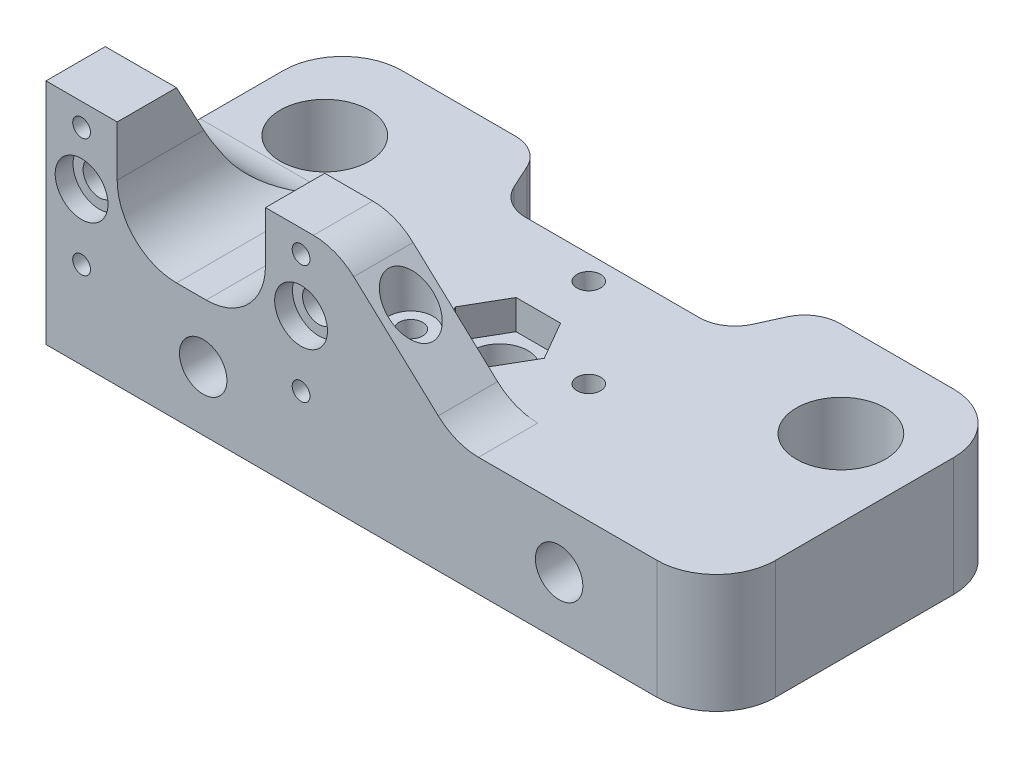
SolidWorks part; units mm, degrees
material "ABS PC"
ref_plane "Front Plane" through (0, 0, 0) normal (0, 0, 1) x (1, 0, 0)
ref_plane "Top Plane" through (0, 0, 0) normal (0, 1, 0) x (1, 0, 0)
ref_plane "Right Plane" through (0, 0, 0) normal (1, 0, 0) x (0, 0, -1)
sketch "Sketch1" plane through (0, 0, 0) normal (0, 1, 0) x (1, 0, 0)
  line L0 (56.5, 0) -> (-56.5, 0)
  line L1 (56.5, 0) -> (56.5, 50)
  line L2 (-56.5, 0) -> (-56.5, 50)
  line L3 (56.5, 50) -> (-56.5, 50)
  dimension "D1" = 113
  dimension "D2" = 50
extrude "Boss-Extrude1" add sketch "Sketch1" along normal blind 20
sketch "Sketch13" plane through (0, 20, 0) normal (0, 1, 0) x (1, 0, 0)
  line L0 (-56.5, 0) -> (-56.5, 10)
  line L1 (-56.5, 0) -> (-44.5, 0)
  line L2 (-56.5, 10) -> (-44.5, 10)
  line L3 (-44.5, 0) -> (-44.5, 10)
  line L4 (-56.5, 50) -> (-56.5, 0) construction
  line L5 (-19.5, 0) -> (-19.5, 10)
  line L6 (-19.5, 0) -> (-7.5, 0)
  line L7 (-19.5, 10) -> (-7.5, 10)
  line L8 (-7.5, 0) -> (-7.5, 10)
  line L10 (-56.5, 0) -> (56.5, 0) construction
  dimension "D1" = 12
  dimension "D2" = 10
  dimension "D3" = 25
extrude "Boss-Extrude2" add sketch "Sketch13" along normal blind 18.5
sketch "Sketch18" plane through (0, 0, -10) normal (0, 0, -1) x (-1, 0, 0)
  line L0 (7.5, 20) -> (-12.5, 20)
  line L1 (-12.5, 20) -> (7.5, 38.5)
  line L2 (7.5, 38.5) -> (7.5, 20)
  dimension "D1" = 20
extrude "Boss-Extrude4" add sketch "Sketch18" against normal blind 10
sketch "Sketch2" plane through (0, 20, 0) normal (0, 1, 0) x (1, 0, 0)
  line L1 (56.5, 0) -> (56.5, 50) construction
  line L3 (56.5, 50) -> (-56.5, 50) construction
  circle A0 centre (-43.5, 34) radius 7.5
  circle A1 centre (43.5, 34) radius 7.5
  circle A2 centre (0, 20) radius 4.75
  circle A3 centre (15, 20) radius 2
  circle A4 centre (-15, 20) radius 2
  circle A5 centre (0, 35) radius 2
  circle A6 centre (0, 5) radius 2
  dimension "D2" = 56.5
  dimension "D3" = 30
  dimension "D5" = 15
  dimension "D6" = 15
  dimension "D1" = 43.5
  dimension "D4" = 43.5
  dimension "D7" = 14
  dimension "D8" = 9.5
  dimension "D9" = 15
  dimension "D10" = 15
  dimension "D11" = 4
  dimension "D12" = 15
  dimension "D13" = 15
extrude "Cut-Extrude1" cut sketch "Sketch2" against normal through all and the other way through all
sketch "Sketch3" plane through (0, 20, 0) normal (0, 1, 0) x (1, 0, 0)
  line L1 (-3.75, 13.5048) -> (3.75, 13.5048)
  line L2 (3.75, 13.5048) -> (7.5, 20)
  line L3 (7.5, 20) -> (3.75, 26.4952)
  line L4 (3.75, 26.4952) -> (-3.75, 26.4952)
  line L5 (-3.75, 26.4952) -> (-7.5, 20)
  line L6 (-7.5, 20) -> (-3.75, 13.5048)
  circle A0 centre (0, 20) radius 6.4952 construction
  circle A1 centre (0, 20) radius 4.75 construction
  dimension "D1" = 15
extrude "Cut-Extrude2" cut sketch "Sketch3" against normal blind 5
sketch "Sketch20" plane through (0, 0, 0) normal (0, -1, 0) x (1, 0, 0)
  circle A0 centre (0, -5) radius 3.75
  dimension "D1" = 7.5
extrude "Cut-Extrude11" cut sketch "Sketch20" against normal blind 15 from offset 28 offset against normal yes
sketch "Sketch5" plane through (0, 0, -50) normal (0, 0, -1) x (-1, 0, 0)
  line L3 (-56.5, 20) -> (-56.5, 0) construction
  line L4 (-56.5, 0) -> (56.5, 0) construction
  circle A0 centre (30, 10) radius 4
  circle A1 centre (-30, 10) radius 4
  dimension "D1" = 8
  dimension "D2" = 60
  dimension "D3" = 26.5
  dimension "D4" = 10
extrude "Cut-Extrude4" cut sketch "Sketch5" against normal through all
sketch "Sketch12" plane through (0, 20, 0) normal (0, 1, 0) x (1, 0, 0)
  line L4 (23.5, 50) -> (18.5, 39)
  line L5 (56.5, 50) -> (-56.5, 50) construction
  line L6 (18.5, 39) -> (-18.5, 39)
  line L7 (-18.5, 39) -> (-23.5, 50)
  line L8 (-23.5, 50) -> (23.5, 50)
  dimension "D2" = 11
  dimension "D3" = 33
  dimension "D4" = 33
  dimension "D5" = 5
  dimension "D6" = 5
extrude "Cut-Extrude6" cut sketch "Sketch12" against normal through all
fillet "Fillet11" radius 10 3 edges at (-56.5, 10, -50) (56.5, 10, -50) (56.5, 10, 0)
fillet "Fillet5" radius 6 4 edges at (-23.5, 10, -50) (23.5, 10, -50) (-18.5, 10, -39) (18.5, 10, -39)
sketch "Sketch14" plane through (0, 0, 0) normal (0, 0, 1) x (1, 0, 0)
  line L1 (-56.5, 38.5) -> (-56.5, 0) construction
  line L4 (-19.5, 20) -> (-44.5, 20) construction
  line L5 (-19.5, 38.5) -> (-19.5, 20) construction
  circle A0 centre (-50.5, 25.7) radius 4.45
  circle A1 centre (-13.5, 25.7) radius 4.45
  dimension "D1" = 5.7
  dimension "D2" = 8.9
  dimension "D4" = 6
  dimension "D3" = 6
extrude "Cut-Extrude7" cut sketch "Sketch14" against normal blind 3
sketch "Sketch17" plane through (-56.5, 0, 0) normal (-1, 0, 0) x (0, 0, 1)
  line L0 (-10, 38.5) -> (-10, 20)
  line L1 (-10, 20) -> (-20, 20)
  line L2 (-40, 20) -> (-10, 20) construction
  line L3 (-20, 20) -> (-10, 38.5)
  dimension "D1" = 10
extrude "Boss-Extrude3" add sketch "Sketch17" against normal blind 12
sketch "Sketch15" plane through (0, 0, -3) normal (0, 0, 1) x (1, 0, 0)
  circle A0 centre (-50.5, 25.7) radius 2.75
  circle A1 centre (-13.5, 25.7) radius 2.75
  circle A2 centre (-50.5, 25.7) radius 4.45 construction
  circle A3 centre (-13.5, 25.7) radius 4.45 construction
  dimension "D1" = 5.5
extrude "Cut-Extrude8" cut sketch "Sketch15" against normal through all
sketch "Sketch16" plane through (0, 0, 0) normal (0, 0, 1) x (1, 0, 0)
  line L1 (-56.5, 38.5) -> (-56.5, 0) construction
  line L5 (-19.5, 38.5) -> (-19.5, 20) construction
  circle A0 centre (-50.5, 34.7) radius 1.5
  circle A1 centre (-50.5, 14.7) radius 1.5
  circle A2 centre (-13.5, 14.7) radius 1.5
  circle A3 centre (-13.5, 34.7) radius 1.5
  circle A4 centre (-50.5, 25.7) radius 2.75 construction
  dimension "D1" = 6
  dimension "D4" = 3
  dimension "D3" = 9
  dimension "D2" = 6
  dimension "D5" = 20
extrude "Cut-Extrude9" cut sketch "Sketch16" against normal blind 16
sketch "Sketch21" plane through (0, 0, 0) normal (0, 0, 1) x (1, 0, 0)
  line L1 (-48.9123, 17.45) -> (-52.0877, 17.45)
  line L2 (-52.0877, 17.45) -> (-53.6754, 14.7)
  line L3 (-53.6754, 14.7) -> (-52.0877, 11.95)
  line L4 (-52.0877, 11.95) -> (-48.9123, 11.95)
  line L5 (-48.9123, 11.95) -> (-47.3246, 14.7)
  line L6 (-47.3246, 14.7) -> (-48.9123, 17.45)
  line L7 (-47.3246, 34.7) -> (-48.9123, 37.45)
  line L8 (-48.9123, 37.45) -> (-52.0877, 37.45)
  line L9 (-52.0877, 37.45) -> (-53.6754, 34.7)
  line L10 (-53.6754, 34.7) -> (-52.0877, 31.95)
  line L11 (-52.0877, 31.95) -> (-48.9123, 31.95)
  line L12 (-48.9123, 31.95) -> (-47.3246, 34.7)
  circle A0 centre (-50.5, 14.7) radius 2.75 construction
  circle A1 centre (-50.5, 34.7) radius 2.75 construction
  dimension "D1" = 5.5
  dimension "D2" = 5.5
extrude "Cut-Extrude12" cut sketch "Sketch21" against normal blind 3 from offset 11 offset against normal yes
sketch "Sketch22" plane through (-56.5, 0, 0) normal (-1, 0, 0) x (0, 0, 1)
  line L0 (-11, 17.45) -> (-11, 11.95)
  line L1 (-11, 17.45) -> (-14, 17.45)
  line L2 (-11, 11.95) -> (-14, 11.95)
  line L3 (-14, 17.45) -> (-14, 11.95)
  line L5 (0, 38.5) -> (0, 0) construction
  line L6 (-40, 0) -> (0, 0) construction
  dimension "D1" = 14
  dimension "D2" = 3
  dimension "D3" = 5.5
  dimension "D4" = 11.95
extrude "Cut-Extrude13" cut sketch "Sketch22" against normal blind 6.5
sketch "Sketch23" plane through (0, 20, 0) normal (0, 1, 0) x (1, 0, 0)
  line L0 (-10.75, 10) -> (-16.25, 10)
  line L1 (-10.75, 10) -> (-10.75, 13)
  line L2 (-16.25, 10) -> (-16.25, 13)
  line L3 (-10.75, 13) -> (-16.25, 13)
  line L4 (12.5, 10) -> (-19.5, 10) construction
  dimension "D1" = 3
  dimension "D2" = 5.5
  dimension "D3" = 3.25
extrude "Cut-Extrude14" cut sketch "Sketch23" against normal blind 8.75
fillet "Fillet13" radius 10 5 edges at (-19.5, 20, -5) (-50.5, 20, -20) (12.5, 20, -5) (-7.5, 38.5, -5)
